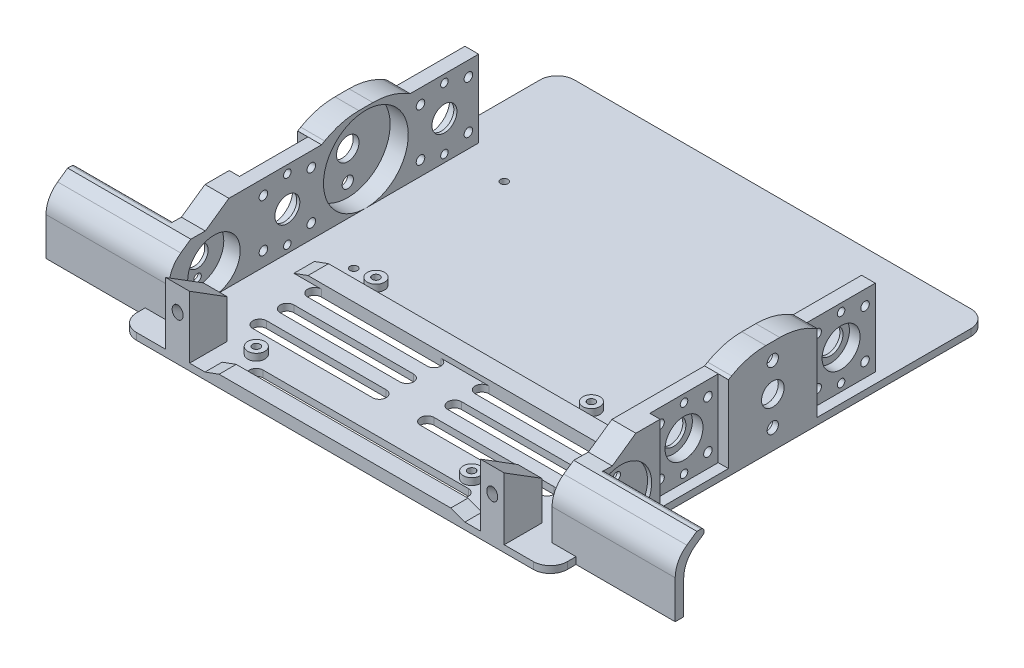
SolidWorks part; units mm, degrees
other "标注1"
sketch "草图81" plane through (-60, 24.5, 62.5) normal (-0.4387, 0.1807, 0.8803) x (0.8455, 0.415, 0.3361)
ref_plane "前视基准面" through (0, 0, 0) normal (0, 0, 1) x (1, 0, 0)
ref_plane "上视基准面" through (0, 0, 0) normal (0, 1, 0) x (1, 0, 0)
ref_plane "右视基准面" through (0, 0, 0) normal (1, 0, 0) x (0, 0, -1)
sketch "草图1" plane through (0, 0, 0) normal (0, 1, 0) x (1, 0, 0)
  line L0 (63, -59) -> (63, 59)
  line L3 (-58, -64) -> (58, -64)
  line L4 (0, -64) -> (35.1535, -64) construction
  line L5 (0, -64) -> (0, 0) construction
  line L8 (-63, -59) -> (-63, 59)
  line L10 (-58, 64) -> (58, 64)
  line L11 (-63, 0) -> (0, 0) construction
  arc A0 (63, 59) -> (58, 64) centre (58, 59) ccw
  arc A3 (58, -64) -> (63, -59) centre (58, -59) ccw
  arc A4 (-58, -64) -> (-63, -59) centre (-58, -59) cw
  arc A7 (-63, 59) -> (-58, 64) centre (-58, 59) cw
  dimension "D2" = 5
  dimension "D3" = 128
  dimension "D4" = 5
  dimension "D1" = 126
extrude "凸台-拉伸1" add sketch "草图1" along normal blind 2
sketch "草图2" plane through (-63, 0, 0) normal (-1, 0, 0) x (0, 0, 1)
  line L0 (-59, 2) -> (59, 2) construction
  line L1 (-14, 2) -> (54, 2)
  line L2 (-14, 2) -> (-14, 24.5)
  line L3 (-14, 24.5) -> (39.0044, 24.5)
  line L4 (54, 2) -> (54, 14)
  line L5 (64, 2) -> (64, 0) construction
  line L6 (54, 14) -> (39.0044, 24.5)
  dimension "D1" = 22.5
  dimension "D2" = 68
  dimension "D3" = 10
  dimension "D4" = 145
  dimension "D5" = 12
extrude "凸台-拉伸2" add sketch "草图2" against normal blind 4
sketch "草图4" plane through (-59, 0, 0) normal (1, 0, 0) x (0, 0, -1)
  line L0 (14, 2) -> (-54, 2) construction
  line L1 (14, 24.5) -> (-11.9, 24.5)
  line L2 (14, 24.5) -> (14, 2)
  line L3 (14, 2) -> (-11.9, 2)
  line L4 (-11.9, 24.5) -> (-11.9, 2)
  dimension "D1" = 25.9
extrude "凸台-拉伸3" add sketch "草图4" along normal blind 3
sketch "草图87" plane through (0, 24.5, 0) normal (0, 1, 0) x (1, 0, 0)
  line L0 (-63, -39.0044) -> (-63, 14) construction
  line L1 (-56, 14) -> (-63, 14)
  line L2 (-56, 14) -> (-56, -11.9)
  line L3 (-56, -11.9) -> (-63, -11.9)
  line L4 (-63, 14) -> (-63, -11.9)
  line L5 (-56, -11.9) -> (-59, -11.9) construction
extrude "凸台-拉伸14" add sketch "草图87" along normal blind 3.2
sketch "草图5" plane through (-63, 0, 0) normal (-1, 0, 0) x (0, 0, 1)
  line L0 (-1.05, 2) -> (-1.05, 14.4) construction
  line L3 (11.9, 2) -> (-14, 2) construction
  circle A0 centre (-1.05, 14.4) radius 12.4
  dimension "D1" = 24.8
extrude "切除-拉伸1" cut sketch "草图5" against normal blind 18 from offset 1.7 contours A0 region at (-63, 14.4, -1.05) offset against normal yes
sketch "草图6" plane through (-61.3, 0, 0) normal (1, 0, 0) x (0, 0, -1)
  line L0 (-30.4164, 14.4) -> (1.05, 14.4) construction
  line L1 (1.05, 14.4) -> (1.05, 22.9) construction
  circle A0 centre (1.05, 14.4) radius 3.3
  circle A1 centre (1.05, 22.9) radius 1.65
  circle A2 centre (1.05, 5.9) radius 1.65
  dimension "D1" = 6.6
  dimension "D2" = 3.3
  dimension "D3" = 17
extrude "切除-拉伸2" cut sketch "草图6" against normal blind 6
sketch3d "3D草图4"
  point P0 (-56, 12.1294, 11.1403)
ref_plane "基准面2" through (0, 0, 0) normal (-1, 0, 0) x (0, 0, 1)
sketch "草图10" plane through (-63, 0, 0) normal (-1, 0, 0) x (0, 0, 1)
  line L1 (54, 2) -> (54, 14)
  line L2 (59, 2) -> (-59, 2) construction
  line L3 (11.9, 2) -> (54, 2) construction
  line L4 (54, 14) -> (39.0044, 24.5)
  line L6 (39.0044, 24.5) -> (11.9, 24.5) construction
  line L7 (39.0044, 24.5) -> (39.0044, 2)
  line L8 (39.0044, 2) -> (54, 2)
extrude "凸台-拉伸4" add sketch "草图10" against normal up to surface (7 mm away)
sketch "草图21" plane through (0, 2, 0) normal (0, 1, 0) x (1, 0, 0)
  line L0 (0, 0) -> (0, 14) construction
  line L1 (0, 14) -> (-40, 14) construction
  circle A0 centre (-40, 14) radius 1.1
  dimension "D3" = 2.2
  dimension "D1" = 14
  dimension "D2" = 40
extrude "切除-拉伸13" cut sketch "草图21" against normal blind 26
sketch "草图22" plane through (0, 2, 0) normal (0, 1, 0) x (1, 0, 0)
  line L0 (0, 0) -> (0, -64) construction
  line L1 (-58, -64) -> (58, -64) construction
  line L2 (-7, -44) -> (-42, -44) construction
  line L3 (-7, -46) -> (-42, -46)
  line L4 (-7, -42) -> (-42, -42)
  line L5 (7, -44) -> (42, -44) construction
  line L6 (7, -46) -> (42, -46)
  line L7 (7, -42) -> (42, -42)
  arc A0 (-7, -46) -> (-7, -42) centre (-7, -44) ccw
  arc A1 (-42, -42) -> (-42, -46) centre (-42, -44) ccw
  arc A2 (7, -46) -> (7, -42) centre (7, -44) cw
  arc A3 (42, -42) -> (42, -46) centre (42, -44) cw
  point P7 (-24.5, -44)
  point P14 (24.5, -44)
  dimension "D1" = 4
  dimension "D2" = 35
  dimension "D3" = 7
  dimension "D4" = 20
sketch "草图26" plane through (-63, 0, 0) normal (-1, 0, 0) x (0, 0, 1)
  line L0 (-14, 27.7) -> (-14, 2) construction
  line L6 (-14, 2) -> (-37, 2)
  line L7 (-14, 2) -> (-14, 24.5)
  line L8 (-14, 24.5) -> (-37, 24.5)
  line L9 (-37, 2) -> (-37, 24.5)
  line L10 (-59, 2) -> (-14, 2) construction
  dimension "D1" = 23
  dimension "D2" = 22.5
extrude "凸台-拉伸5" add sketch "草图26" against normal up to surface (4 mm away) up to face at (-59, 13.25, 25.4522)
ref_plane "基准面1" through (0, 0, -1.05) normal (0, 0, 1) x (1, 0, 0)
sketch "草图27" plane through (-63, 0, 0) normal (-1, 0, 0) x (0, 0, 1)
  line L0 (-1.05, 14.4) -> (21.9187, 13.2) construction
  line L1 (21.9187, 13.2) -> (21.9187, 14.4) construction
  line L2 (-1.05, 14.4) -> (21.9187, 14.4) construction
  circle A0 centre (21.9187, 13.2) radius 5.53
  dimension "D3" = 11.06
  dimension "D1" = 23
  dimension "D2" = 1.2
extrude "切除-拉伸14" cut sketch "草图27" against normal blind 2.65
sketch "草图28" plane through (-60.35, 0, 0) normal (-1, 0, 0) x (0, 0, 1)
  circle A0 centre (21.9187, 13.2) radius 3.65
  dimension "D1" = 7.3
extrude "切除-拉伸15" cut sketch "草图28" against normal blind 2.65
sketch "草图29" plane through (-63, 0, 0) normal (-1, 0, 0) x (0, 0, 1)
  line L1 (28.9187, 20.2) -> (14.9187, 20.2) construction
  line L2 (28.9187, 20.2) -> (28.9187, 6.2) construction
  line L3 (28.9187, 6.2) -> (14.9187, 6.2) construction
  line L4 (14.9187, 20.2) -> (14.9187, 6.2) construction
  line L5 (28.9187, 20.2) -> (14.9187, 6.2) construction
  line L6 (28.9187, 6.2) -> (14.9187, 20.2) construction
  circle A0 centre (28.9187, 20.2) radius 1.25
  circle A1 centre (14.9187, 20.2) radius 1.25
  circle A2 centre (14.9187, 6.2) radius 1.25
  circle A3 centre (28.9187, 6.2) radius 1.25
  point P0 (21.9187, 13.2)
  dimension "D2" = 2.5
  dimension "D3" = 2.5
  dimension "D4" = 2.5
  dimension "D5" = 2.5
  dimension "D1" = 14
extrude "切除-拉伸16" cut sketch "草图29" against normal blind 10
sketch "草图33" plane through (-59, 0, 0) normal (1, 0, 0) x (0, 0, -1)
  line L4 (-39.0044, 24.5) -> (-39.0044, 2)
  line L5 (-39.0044, 2) -> (-11.9, 2)
  line L6 (-11.9, 2) -> (-11.9, 24.5)
  line L7 (-39.0044, 24.5) -> (-39.0044, 2)
  line L9 (-39.0044, 2) -> (-11.9, 2)
  line L10 (-11.9, 2) -> (-11.9, 24.5)
  line L12 (-11.9, 24.5) -> (-39.0044, 24.5)
  line L14 (-11.9, 24.5) -> (-39.0044, 24.5)
  circle A0 centre (-21.9187, 13.2) radius 3.65 construction
  circle A1 centre (-21.9187, 13.2) radius 3.65
  circle A2 centre (-28.9187, 6.2) radius 1.25 construction
  circle A3 centre (-28.9187, 6.2) radius 1.25
  circle A4 centre (-28.9187, 20.2) radius 1.25 construction
  circle A5 centre (-28.9187, 20.2) radius 1.25
  circle A6 centre (-14.9187, 20.2) radius 1.25 construction
  circle A7 centre (-14.9187, 20.2) radius 1.25
  circle A8 centre (-14.9187, 6.2) radius 1.25 construction
  circle A9 centre (-14.9187, 6.2) radius 1.25
  dimension "D1" = 0
extrude "凸台-拉伸6" add sketch "草图33" along normal blind 3
sketch "草图35" plane through (-63, 0, 0) normal (-1, 0, 0) x (0, 0, 1)
  line L0 (11.9187, 26) -> (31.9187, 26)
  line L2 (39.0044, 2) -> (11.9, 2) construction
  line L3 (31.9187, 2) -> (11.9187, 2)
  line L5 (11.9187, 2) -> (11.9187, 26)
  line L8 (31.9187, 2) -> (31.9187, 26)
  line L9 (21.9187, 13.2) -> (21.9187, 19.3052) construction
  dimension "D1" = 20
extrude "切除-拉伸17" cut sketch "草图35" against normal blind 3
sketch "草图36" plane through (-60, 0, 0) normal (-1, 0, 0) x (0, 0, 1)
  circle A0 centre (21.9187, 13.2) radius 5.55
  dimension "D1" = 11.1
extrude "切除-拉伸18" cut sketch "草图36" against normal blind 3.1
sketch "草图37" plane through (-60, 0, 0) normal (-1, 0, 0) x (0, 0, 1)
  line L0 (21.9187, 4.2) -> (21.9187, 22.2) construction
  circle A0 centre (21.9187, 22.2) radius 1.1
  circle A1 centre (21.9187, 4.2) radius 1.1
  point P5 (21.9187, 13.2)
  dimension "D2" = 2.2
  dimension "D3" = 2.2
  dimension "D1" = 18
extrude "切除-拉伸19" cut sketch "草图37" against normal blind 26.5
mirror "镜向1" about plane through (0, 0, -1.05) normal (0, 0, 1) of "凸台-拉伸6", "切除-拉伸19", "切除-拉伸18", "切除-拉伸17", "切除-拉伸16", "切除-拉伸15", "切除-拉伸14"
sketch "草图39" plane through (-56, 0, 0) normal (1, 0, 0) x (0, 0, -1)
  line L0 (0, 2) -> (-64, 2) construction
  circle A0 centre (-43.3811, 9.675) radius 7.675
  circle A1 centre (-21.9187, 13.2) radius 3.65 construction
  dimension "D1" = 15.35
  dimension "D2" = 21.75
extrude "切除-拉伸20" cut sketch "草图39" against normal blind 4.8
sketch "草图41" plane through (-63, 0, 0) normal (-1, 0, 0) x (0, 0, 1)
  circle A0 centre (43.3811, 9.675) radius 9
  dimension "D1" = 18
extrude "切除-拉伸21" cut sketch "草图41" against normal blind 1.2
sketch "草图90" plane through (-63, 0, 0) normal (-1, 0, 0) x (0, 0, 1)
  line L0 (-59, 2) -> (-37, 2) construction
  line L1 (-34.0187, 24.5) -> (-53.8357, 24.5)
  line L2 (-34.0187, 24.5) -> (-34.0187, 2)
  line L3 (-34.0187, 2) -> (-53.8357, 2)
  line L4 (-53.8357, 24.5) -> (-53.8357, 2)
extrude "切除-拉伸49" cut sketch "草图90" against normal blind 14
sketch "草图42" plane through (-61.8, 0, 0) normal (-1, 0, 0) x (0, 0, 1)
  line L0 (43.3811, 9.675) -> (43.3811, 15.175) construction
  line L1 (43.3811, 9.675) -> (35.1091, 9.675) construction
  circle A0 centre (43.3811, 9.675) radius 3.1
  circle A1 centre (43.3811, 15.175) radius 1.1
  circle A2 centre (43.3811, 4.175) radius 1.1
  dimension "D1" = 6.2
  dimension "D2" = 2.2
  dimension "D3" = 11
extrude "切除-拉伸22" cut sketch "草图42" against normal blind 10
chamfer "倒角1" distance 3.2 angle 60 2 edges at (-59.5, 27.7, -14) (-59.5, 27.7, 11.9) first distance on face at (-59.5, 26.1, -14) first distance on face at (-59.5, 26.1, 11.9)
fillet "圆角1" radius 20 2 edges at (-59.5, 27.7, -8.4574) (-59.5, 27.7, 6.3574)
mirror "镜向15" about plane through (0, 0, 0) normal (1, 0, 0) of bodies 149
sketch "草图43" plane through (-61.8, 0, 0) normal (-1, 0, 0) x (0, 0, 1)
  circle A0 centre (43.3811, 9.675) radius 9
extrude "切除-拉伸23" cut sketch "草图43" along normal blind 67
sketch "草图49" plane through (0, 2, 0) normal (0, 1, 0) x (1, 0, 0)
  line L0 (0, -64) -> (0, 12) construction
  line L1 (58, 64) -> (-58, 64) construction
  line L2 (-49, 34) -> (49, 34)
  line L3 (-49, 34) -> (-49, -10)
  line L4 (-49, -10) -> (49, -10)
  line L5 (49, 34) -> (49, -10)
  line L6 (-49, 34) -> (49, -10) construction
  line L7 (-49, -10) -> (49, 34) construction
  dimension "D1" = 44
  dimension "D2" = 98
  dimension "D3" = 30
sketch "草图53" plane through (0, 2, 0) normal (0, 1, 0) x (1, 0, 0)
  line L0 (0, -64) -> (0, -58.5) construction
  line L1 (0, 0) -> (0, -64) construction
  line L2 (-46, -58.5) -> (46, -58.5) construction
  line L4 (-49.5, -53) -> (-42.5, -53)
  line L5 (-49.5, -53) -> (-49.5, -64)
  line L6 (-49.5, -64) -> (-42.5, -64)
  line L7 (-42.5, -53) -> (-42.5, -64)
  line L8 (-49.5, -53) -> (-42.5, -64) construction
  line L9 (-49.5, -64) -> (-42.5, -53) construction
  point P8 (0, -58.5)
  dimension "D1" = 46
  dimension "D2" = 7
  dimension "D3" = 11
  dimension "D4" = 5.5
extrude "切除-拉伸28" cut sketch "草图53" against normal blind 0.8
extrude "切除-拉伸30" cut sketch "草图22" against normal blind 10
pattern_linear "阵列(线性)1" count 2 spacing 8 along (0, 0, -1) of "切除-拉伸30"
sketch "草图59" plane through (0, 2, 0) normal (0, 1, 0) x (1, 0, 0)
  line L1 (-58, -64) -> (-49.5, -64) construction
  line L2 (-53.75, -64) -> (-53.75, -45.8488) construction
  line L3 (-35, -17) -> (28, -17)
  line L4 (-35, -17) -> (-35, -52)
  line L5 (-35, -52) -> (28, -52)
  line L6 (28, -17) -> (28, -52)
  line L7 (-35, -17) -> (28, -52) construction
  line L8 (-35, -52) -> (28, -17) construction
  line L10 (0, 15.235) -> (0, -15.235) construction
  line L11 (-42.5, -64) -> (58, -64) construction
  point P12 (-3.5, -34.5)
  dimension "D1" = 35
  dimension "D2" = 63
  dimension "D3" = 3.5
  dimension "D4" = 12
hole_wizard "大小mm 暗销孔2" positions "3D草图2" profile "草图60" hole size "Ø1.0" standard "GB" end condition through all
sketch3d "3D草图2"
  point P4 (28, 2, 52)
  point P7 (28, 2, 17)
  point P10 (-35, 2, 17)
  point P13 (-35, 2, 52)
sketch "草图60" plane through (28, 2, 52) normal (1, 0, 0) x (0, 0, 1)
  line L0 (0, 0) -> (0, 2)
  line L1 (0, 2) -> (1.1, 2)
  line L2 (1.1, 2) -> (1.1, 0)
  line L5 (1.1, 0) -> (0, 0)
  line L11 (0, -6.35) -> (0, 107.95) construction
  dimension "通孔孔直径" = 2.2
  dimension "通孔孔深度" = 2
sketch "草图67" plane through (61.8, 0, 0) normal (1, 0, 0) x (0, 0, -1)
  circle A0 centre (-43.3811, 9.675) radius 9
  dimension "D1" = 18
extrude "切除-拉伸39" cut sketch "草图67" along normal blind 10
sketch "草图69" plane through (0, 2, 0) normal (0, 1, 0) x (1, 0, 0)
  line L0 (0, 64) -> (0, 0) construction
  line L1 (58, 64) -> (-58, 64) construction
  line L2 (0, 6) -> (3.3378, 6) construction
  line L3 (-42.5, 28) -> (42.5, 28)
  line L4 (-42.5, 28) -> (-42.5, -16)
  line L5 (-42.5, -16) -> (42.5, -16)
  line L6 (42.5, 28) -> (42.5, -16)
  line L7 (-42.5, 28) -> (42.5, -16) construction
  line L8 (-42.5, -16) -> (42.5, 28) construction
  dimension "D1" = 44
  dimension "D2" = 85
  dimension "D3" = 6
hole_wizard "大小mm 暗销孔3" positions "3D草图3" profile "草图70" hole size "Ø1.0" standard "GB" end condition through all
sketch3d "3D草图3"
  point P0 (-42.5, 2, -28)
  point P3 (-42.5, 2, 16)
  point P6 (42.5, 2, 16)
  point P9 (42.5, 2, -28)
sketch "草图70" plane through (-42.5, 2, -28) normal (1, 0, 0) x (0, 0, 1)
  line L0 (0, 0) -> (0, 2)
  line L1 (0, 2) -> (1.1, 2)
  line L2 (1.1, 2) -> (1.1, 0)
  line L5 (1.1, 0) -> (0, 0)
  line L11 (0, -6.35) -> (0, 107.95) construction
  dimension "通孔孔直径" = 2.2
  dimension "通孔孔深度" = 2
sketch "草图71" plane through (0, 2, 0) normal (0, 1, 0) x (1, 0, 0)
  line L0 (-30, -57) -> (30, -57) construction
  line L1 (-30, -55) -> (30, -55)
  line L2 (-30, -59) -> (30, -59)
  line L4 (-58, -64) -> (-49.5, -64) construction
  line L5 (0, 15.235) -> (0, -15.235) construction
  arc A0 (-30, -55) -> (-30, -59) centre (-30, -57) ccw
  arc A1 (30, -59) -> (30, -55) centre (30, -57) ccw
  point P2 (0, -57)
  dimension "D1" = 4
  dimension "D2" = 60
  dimension "D3" = 5
extrude "切除-拉伸42" cut sketch "草图71" against normal blind 10
sketch "草图72" plane through (0, 2, 0) normal (0, 1, 0) x (1, 0, 0)
  line L0 (-42, -28) -> (-7, -28) construction
  line L1 (-42, -26) -> (-7, -26)
  line L2 (-42, -30) -> (-7, -30)
  line L3 (-5, -28) -> (-5, -36) construction
  line L4 (-7, -34) -> (-42, -34) construction
  line L5 (0, 0) -> (0, -17) construction
  line L6 (-35, -17) -> (28, -17) construction
  line L7 (42, -28) -> (7, -28) construction
  line L8 (42, -26) -> (7, -26)
  line L9 (42, -30) -> (7, -30)
  line L10 (5, -28) -> (5, -36) construction
  arc A0 (-42, -26) -> (-42, -30) centre (-42, -28) ccw
  arc A1 (-7, -30) -> (-7, -26) centre (-7, -28) ccw
  arc A2 (-7, -38) -> (-7, -34) centre (-7, -36) ccw construction
  arc A3 (42, -26) -> (42, -30) centre (42, -28) cw
  arc A4 (7, -30) -> (7, -26) centre (7, -28) cw
  point P2 (-24.5, -28)
  point P21 (24.5, -28)
  dimension "D1" = 4
  dimension "D2" = 35
  dimension "D3" = 4
extrude "切除-拉伸43" cut sketch "草图72" against normal blind 10
sketch "草图75" plane through (0, 0, 59) normal (0, 0, -1) x (-1, 0, 0)
  line L0 (0, 0) -> (0, 4.8259) construction
  line L1 (38, 0.9352) -> (-38, 0.9352)
  line L2 (-58, 0) -> (58, 0) construction
  line L3 (-38, 0.9352) -> (-38, 2)
  line L4 (35, 2) -> (-28, 2) construction
  line L5 (-38, 2) -> (-33.8788, 3.5)
  line L6 (-33.8788, 3.5) -> (33.8788, 3.5)
  line L7 (38, 2) -> (33.8788, 3.5)
  line L8 (38, 0.9352) -> (38, 2)
  point P12 (0, 3.5)
  point P14 (0, 0.9352)
  dimension "D1" = 20
  dimension "D2" = 1.5
  dimension "D3" = 76
extrude "凸台-拉伸7" add sketch "草图75" against normal up to surface (5 mm away) up to face at (-23, 1.3, 64)
sketch "草图76" plane through (0, 0, 26) normal (0, 0, 1) x (1, 0, 0)
  line L0 (0, 0) -> (0, 8.9516) construction
  line L1 (50, 0.6922) -> (-50, 0.6922)
  line L2 (-50, 0.6922) -> (-50, 2)
  line L3 (-35, 2) -> (28, 2) construction
  line L4 (-50, 2) -> (-45.8788, 3.5)
  line L5 (33.8788, 3.5) -> (-33.8788, 3.5) construction
  line L6 (-45.8788, 3.5) -> (45.8788, 3.5)
  line L7 (50, 2) -> (45.8788, 3.5)
  line L8 (50, 0.6922) -> (50, 2)
  point P13 (0, 3.5)
  point P15 (0, 0.6922)
  dimension "D1" = 20
  dimension "D2" = 100
extrude "凸台-拉伸8" add sketch "草图76" against normal blind 6
sketch "草图78" plane through (0, 2, 0) normal (0, 1, 0) x (1, 0, 0)
  circle A0 centre (-35, -17) radius 2.5
  circle A1 centre (-35, -17) radius 1.1
  circle A2 centre (-35, -52) radius 2.5
  circle A3 centre (-35, -52) radius 1.1
  circle A4 centre (28, -52) radius 2.5
  circle A5 centre (28, -52) radius 1.1
  circle A6 centre (28, -17) radius 2.5
  circle A7 centre (28, -17) radius 1.1
  dimension "D1" = 5
  dimension "D2" = 2.2
  dimension "D3" = 5
  dimension "D4" = 2.2
  dimension "D5" = 5
  dimension "D6" = 2.2
  dimension "D7" = 5
  dimension "D8" = 2.2
extrude "凸台-拉伸11" add sketch "草图78" along normal blind 2
sketch "草图114" plane through (0, 1.2, 0) normal (0, 1, 0) x (1, 0, 0)
  line L4 (-42.5, -64) -> (-42.5, -53)
  line L5 (-42.5, -53) -> (-49.5, -53)
  line L6 (-49.5, -53) -> (-49.5, -64)
  line L7 (-49.5, -64) -> (-42.5, -64)
  line L8 (-42.5, -64) -> (-42.5, -53)
  line L9 (-42.5, -53) -> (-49.5, -53)
  line L10 (-49.5, -53) -> (-49.5, -64)
  line L11 (-49.5, -64) -> (-42.5, -64)
  dimension "D1" = 0
extrude "凸台-拉伸17" add sketch "草图114" along normal blind 19
sketch "草图115" plane through (-49.5, 0, 0) normal (-1, 0, 0) x (0, 0, 1)
  line L0 (64, 20.2) -> (53, 13.3264)
  line L1 (53, 20.2) -> (53, 2) construction
  line L2 (53, 13.3264) -> (53, 20.2)
  line L3 (53, 20.2) -> (64, 20.2)
  dimension "D1" = 32
extrude "切除-拉伸52" cut sketch "草图115" against normal blind 19
ref_plane "基准面4" through (-46, 0, 0) normal (-1, 0, 0) x (0, 0, 1)
sketch "草图116" plane through (-46, 0, 0) normal (-1, 0, 0) x (0, 0, 1)
  line L0 (69.7162, 16.6968) -> (54.1902, 6.9951)
  line L1 (53, 13.3264) -> (64, 20.2) construction
  dimension "D1" = 6
sweep "切除-扫描2" cut path "草图116" circular profile diameter 3.2 parameters "D3"=3.2
mirror "镜向23" about plane through (0, 0, 0) normal (1, 0, 0) of "凸台-拉伸17", "切除-拉伸52", "切除-扫描2"
sketch "草图133" plane through (-56, 0, 0) normal (1, 0, 0) x (0, 0, -1)
  line L2 (-56.5, 15.3014) -> (-50.1691, 19.7344)
  line L4 (-54, 14) -> (-39.0044, 24.5) construction
  line L5 (-45.915, 19.6612) -> (-54, 14)
  line L6 (-54, 14) -> (-54, 0)
  line L7 (59, 0) -> (-59, 0) construction
  line L8 (-54, 0) -> (-56.5, 0)
  line L10 (-56.5, 0) -> (-56.5, 15.3014)
  line L11 (-50.1691, 19.7344) -> (-45.9035, 19.6693)
  line L12 (-54, 14) -> (-39.0044, 24.5) construction
  line L13 (-45.9035, 19.6693) -> (-45.915, 19.6612)
  dimension "D1" = 2.5
  dimension "D2" = 2.5
extrude "凸台-拉伸19" add sketch "草图133" against normal blind 36
fillet "圆角4" radius 8 2 edges at (-77.5, 14, 54) (-74, 15.3014, 56.5)
sketch "草图138" plane through (0, 0, 0) normal (0, -1, 0) x (1, 0, 0)
  line L0 (-92, 54.6812) -> (-92, 54)
  line L1 (-92, 56.5) -> (-92, 54) construction
  line L2 (-92, 54) -> (-63, 48.6859)
  line L5 (-63, 48.6859) -> (-61.1168, 48.6859)
  line L6 (-61.1168, 48.6859) -> (-61.1168, 54.6812)
  line L7 (-61.1168, 54.6812) -> (-92, 54.6812)
  line L8 (-63, -59) -> (-63, 54) construction
extrude "凸台-拉伸21" add sketch "草图138" against normal blind 2
fillet "圆角5" radius 1 1 edges at (-77.5, 19.6693, 45.9035)
mirror "镜向26" about plane through (0, 0, 0) normal (1, 0, 0) of "凸台-拉伸19", "圆角4", "凸台-拉伸21", "圆角5"
